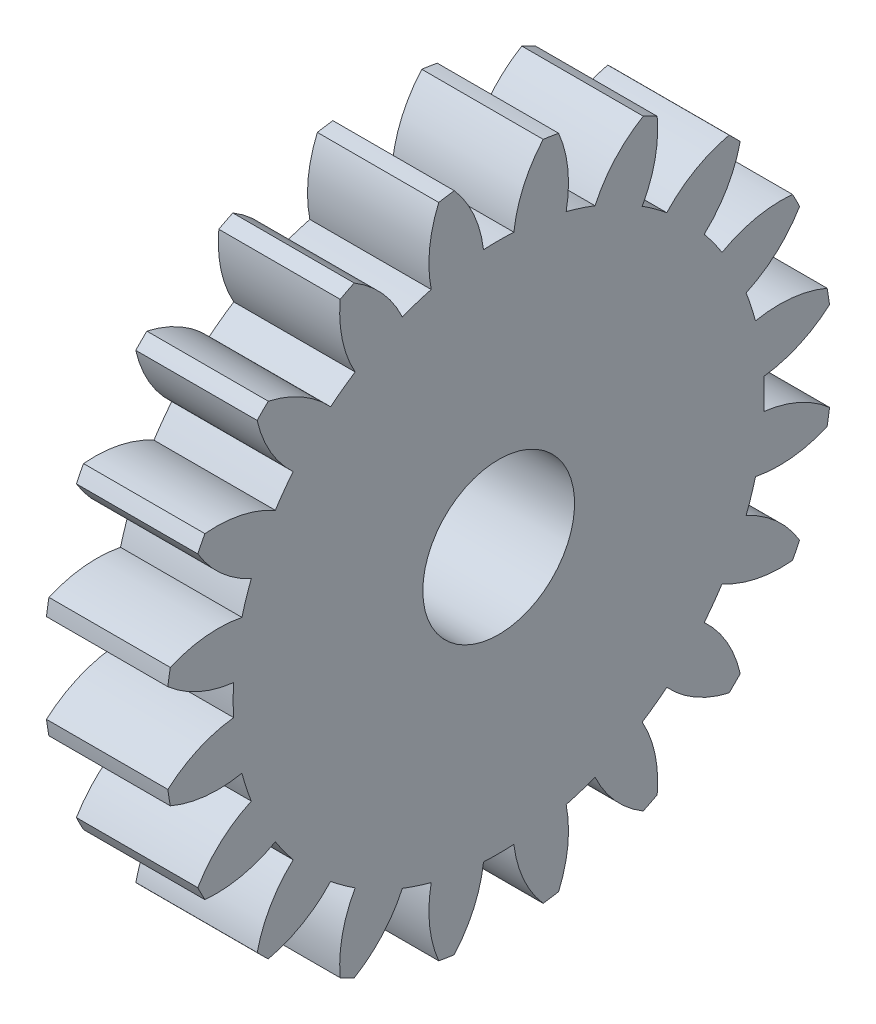
SolidWorks part; units mm, degrees
ref_plane "Plane1" through (0, 0, 0) normal (0, 0, 1) x (1, 0, 0)
ref_plane "Plane2" through (0, 0, 0) normal (0, 1, 0) x (1, 0, 0)
ref_plane "Plane3" through (0, 0, 0) normal (1, 0, 0) x (0, 0, -1)
other "Configuration Table"
sketch "HoldingSke" plane through (0, 0, 0) normal (0, 1, 0) x (1, 0, 0)
  line L0 (0, 0) -> (0.9397, -0.342)
  line L1 (-15, 0) -> (100, 0) construction
  line L2 (0, 0) -> (-2.1039, 2.3779)
  line L3 (0, 0) -> (-11.863, 4.5341)
  line L4 (0, 0) -> (8.1152, 2.9537)
  line L5 (0, 0) -> (-46.8476, -17.4728)
  line L6 (0, 0) -> (-3.3159, -2.2372)
  line L7 (-2.1039, 2.3779) -> (8.6586, 51.2059)
  line L8 (-76.2, 54.61) -> (-75.3, 54.61)
  line L9 (-71.009, 38.7566) -> (-53.1078, 45.2721)
  line L10 (-76.2, 71.12) -> (104.1128, 71.12)
  line L11 (0, 0) -> (-4, 0)
  line L12 (-76.2, 101.6) -> (-76.162, 101.6)
  line L13 (24.9733, 27.94) -> (52.9518, 28.4284)
  line L14 (24.9733, 27.94) -> (24.9743, 27.94)
  line L15 (24.9733, 27.94) -> (100.4006, 29.5858)
  line L16 (-63.627, -1) -> (-12.827, -1)
  circle A0 centre (0, 0) radius 2.5
  circle A1 centre (0, 0) radius 8.749
  circle A2 centre (0, 0) radius 37.5
  circle A3 centre (0, 0) radius 2.5
  dimension "Num_teeth" = 20
  dimension "Pitch_radius" = 180.3128
  dimension "Width" = 4
  dimension "Thickness" = 4
sketch "BasProSke" plane through (0, 0, 0) normal (0, 1, 0) x (1, 0, 0)
  line L0 (-10, 0) -> (60, 0) construction
  line L1 (0, 0) -> (0, 11)
  line L2 (0, 0) -> (4, 0)
  line L3 (4, 0) -> (4, 11)
  line L4 (4, 11) -> (0, 11)
  dimension "Thickness" = 4
  dimension "Diameter" = 22
revolve "Base-Revolve" add sketch "BasProSke" angle 360 about L0
sketch "TooCutSke" plane through (0, 0, 0) normal (1, 0, 0) x (0, 0, -1)
  line L1 (0, 0) -> (0, 107) construction
  line L2 (0, 0) -> (-0.8511, 9.9637) construction
  line L3 (0, 0) -> (-3.1206, 19.7028) construction
  line L4 (-0.8511, 9.9637) -> (-1.5603, 9.8514) construction
  arc A0 (0.4999, 8.7347) -> (-0.4999, 8.7347) centre (0, 0) ccw
  arc A1 (1.4852, 10.9249) -> (-1.4852, 10.9249) centre (0, 0) ccw
  circle A2 centre (0, 0) radius 10 construction
  circle A3 centre (0, 0) radius 9.3969 construction
  arc A4 (-0.4999, 8.7347) -> (-1.4852, 10.9249) centre (-4.4722, 8.2645) ccw
  arc A5 (1.4852, 10.9249) -> (0.4999, 8.7347) centre (4.4722, 8.2645) ccw
extrude "ToothCut" cut sketch "TooCutSke" along normal through all
fillet "Breaks" [suppressed] radius 0.02 tangent propagation no
fillet "RootFillets" [suppressed] radius 0.251
pattern_circular "TeethCuts" count 20 every 18 about axis through (-10, 0, 0) along (1, 0, 0) of "ToothCut", "RootFillets", "Breaks"
sketch "HubNeaOneSke" plane through (0, 0, 0) normal (-1, 0, 0) x (0, 0, 1)
  circle A0 centre (0, 0) radius 8.749
  dimension "Diameter" = 17.498
extrude "HubNearOne" [suppressed] add sketch "HubNeaOneSke" along normal blind 46.0001
sketch "HubNeaBotSke" plane through (0, 0, 0) normal (-1, 0, 0) x (0, 0, 1)
  circle A0 centre (0, 0) radius 8.749
  dimension "Diameter" = 17.498
extrude "HubNearBoth" [suppressed] add sketch "HubNeaBotSke" along normal blind 23
ref_plane "FarPln" through (4, 0, 0) normal (1, 0, 0) x (0, 0, -1)
sketch "HubFarSke" plane through (4, 0, 0) normal (1, 0, 0) x (0, 0, -1)
  circle A0 centre (0, 0) radius 8.749
  dimension "Diameter" = 17.498
extrude "HubFar" [suppressed] add sketch "HubFarSke" along normal blind 23
sketch "BorSke" plane through (0, 0, 0) normal (1, 0, 0) x (0, 0, -1)
  circle A0 centre (0, 0) radius 2.5
  dimension "Diameter" = 5
extrude "Bore" cut sketch "BorSke" along normal mid plane 100.0001
sketch "KeySke" plane through (0, 0, 0) normal (1, 0, 0) x (0, 0, -1)
  line L0 (-1, 0) -> (-1, 3.4)
  line L1 (-1, 3.4) -> (1, 3.4)
  line L2 (1, 3.4) -> (1, 0)
  line L3 (0, 0) -> (0, 34) construction
  line L4 (-1, 0) -> (1, 0)
  dimension "Width" = 2
extrude "Keyway" [suppressed] cut sketch "KeySke" along normal mid plane 100.0001
pattern_circular "Keyway2" [suppressed] count 2 every 90 about axis through (-10, 0, 0) along (1, 0, 0)
equation "' \"Module@HoldingSke\" = 6.35"
equation "' \"Num_teeth@HoldingSke\" = 12"
equation "' \"Ap@HoldingSke\" =  20"
equation "' \"Ap@HoldingSke\" = 20"
equation "' \"Width@HoldingSke\" = 0.5 * 25.4"
equation "' \"Hub_dia@HoldingSke\"= 1 * 25.4"
equation "' \"Hub_dia@HoldingSke\" = 1 * 25.4"
equation "' \"Overall_len@HoldingSke\" = 1.0 * 25.4"
equation "' \"Bore@HoldingSke\" = 0.75 * 25.4"
equation "' \"T_dim@HoldingSke\" = 0.1 * 25.4"
equation "' \"Width@KeySke\" = 0.25 * 25.4"
equation "' \"Show_teeth@HoldingSke\" = 13"
equation "' \"Backlash@HoldingSke\" = 0.009 * 25.4"
equation "' \"Addendum_fac@HoldingSke\" = 1.0"
equation "' \"Dedendum_fac@HoldingSke\" = 1.25"
equation "' \"Dedendum_add@HoldingSke\" = 0.00005 * 25.4"
equation "' \"Clearance_fac@HoldingSke\" = 0.25"
equation "\"Pitch@HoldingSke\" = 1 / \"Module@HoldingSke\""
equation "\"Overcut_dia@TooCutSke\" = (\"Num_teeth@HoldingSke\" + 2 * \"Addendum_fac@HoldingSke\") / \"Pitch@HoldingSke\" + 0.002 * 25.4"
equation "\"Pitch_dia@TooCutSke\" = \"Num_teeth@HoldingSke\" / \"Pitch@HoldingSke\""
equation "\"Base_dia@TooCutSke\" = \"Num_teeth@HoldingSke\" / \"Pitch@HoldingSke\" * cos((\"Ap@HoldingSke\"  * 3.14159265 / 180))"
equation "\"Root_dia@TooCutSke\" = (\"Num_teeth@HoldingSke\" + 2) / \"Pitch@HoldingSke\" - 2 * (\"Addendum_fac@HoldingSke\" + \"Dedendum_fac@HoldingSke\") / \"Pitch@HoldingSke\" - \"Dedendum_add@HoldingSke\" * 2"
equation "\"Half_ang@TooCutSke\" = 180 / \"Num_teeth@HoldingSke\""
equation "\"Half_CT@TooCutSke\" = \"Num_teeth@HoldingSke\" / \"Pitch@HoldingSke\" * sin((3.14159265 / 2 / \"Num_teeth@HoldingSke\")) / 2 - 7 * \"Backlash@HoldingSke\" / 4"
equation "\"Flank_rad@TooCutSke\" = \"Num_teeth@HoldingSke\" / \"Pitch@HoldingSke\" / 5"
equation "\"Radius@RootFillets\" = \"Clearance_fac@HoldingSke\" / \"Pitch@HoldingSke\" + \"Dedendum_add@HoldingSke\""
equation "\"Break_rad@Breaks\" = 0.02 / \"Pitch@HoldingSke\""
equation "\"Thickness@HoldingSke\" = \"Width@HoldingSke\""
equation "\"OAL@HoldingSke\" = \"Thickness@HoldingSke\""
equation "\"MHD@HoldingSke\" = (\"Num_teeth@HoldingSke\" + 2) / \"Pitch@HoldingSke\" - 2 * (\"Addendum_fac@HoldingSke\" + \"Dedendum_fac@HoldingSke\")  / \"Pitch@HoldingSke\" - \"Dedendum_add@HoldingSke\" * 2"
equation "\"MBD@HoldingSke\" = (\"Num_teeth@HoldingSke\" + 2) / \"Pitch@HoldingSke\" - 2 * (\"Addendum_fac@HoldingSke\" + \"Dedendum_fac@HoldingSke\")  / \"Pitch@HoldingSke\" - \"Dedendum_add@HoldingSke\" * 2 - 0.002 * 25.4"
equation "\"MHD@HoldingSke\" = ((sgn( \"MHD@HoldingSke\" - \"Hub_dia@HoldingSke\" )-1)*( \"MHD@HoldingSke\" - \"Hub_dia@HoldingSke\" ))/-2+ \"Hub_dia@HoldingSke\""
equation "\"MBD@HoldingSke\" = ((sgn( \"MBD@HoldingSke\" - \"Bore@HoldingSke\" )-1)*( \"MBD@HoldingSke\" - \"Bore@HoldingSke\" ))/-2+ \"Bore@HoldingSke\""
equation "\"OAL@HoldingSke\" = ((sgn( \"OAL@HoldingSke\" - \"Overall_len@HoldingSke\" )+1)*( \"OAL@HoldingSke\" - \"Overall_len@HoldingSke\" ))/2 + \"Overall_len@HoldingSke\" + 0.000002 * 25.4"
equation "\"Num_teeth@TeethCuts\" = int( \"Show_teeth@HoldingSke\" ) + 1"
equation "\"Num_teeth@TeethCuts\" = ((sgn( \"Num_teeth@TeethCuts\" - \"Num_teeth@HoldingSke\" )-1)*( \"Num_teeth@TeethCuts\" - \"Num_teeth@HoldingSke\" ))/-2+ \"Num_teeth@HoldingSke\""
equation "\"Num_teeth@TeethCuts\" = ((sgn( \"Num_teeth@TeethCuts\" - 2.0)+1)*( \"Num_teeth@TeethCuts\" - 2.0))/2 +2.0"
equation "\"Angle@TeethCuts\" = 360.0 / \"Num_teeth@HoldingSke\""
equation "\"Diameter@BasProSke\" = (\"Num_teeth@HoldingSke\" + 2 * \"Addendum_fac@HoldingSke\") / \"Pitch@HoldingSke\""
equation "\"Thickness@BasProSke\"  = \"Thickness@HoldingSke\""
equation "' \"Fillet_rad@BasProSke\" =  \"Thickness@HoldingSke\" * 0.05"
equation "' \"Fillet_rad@BasProSke\" = \"Thickness@HoldingSke\" * 0.05"
equation "\"MHD@HoldingSke\" = ((sgn( \"MHD@HoldingSke\" - \"Root_dia@TooCutSke\" )-1)*( \"MHD@HoldingSke\" - \"Root_dia@TooCutSke\" ))/-2+ \"Root_dia@TooCutSke\""
equation "\"Diameter@HubNeaOneSke\" = \"MHD@HoldingSke\""
equation "\"Length@HubNearOne\" = \"OAL@HoldingSke\" - \"Thickness@BasProSke\""
equation "\"Diameter@HubNeaBotSke\" = \"MHD@HoldingSke\""
equation "\"Length@HubNearBoth\" = ( \"OAL@HoldingSke\" - \"Thickness@BasProSke\" ) / 2.0"
equation "\"Thickness@FarPln\" = \"Thickness@BasProSke\""
equation "\"Diameter@HubFarSke\" = \"MHD@HoldingSke\""
equation "\"Length@HubFar\" = ( \"OAL@HoldingSke\" - \"Thickness@BasProSke\" ) / 2.0"
equation "\"Diameter@BorSke\" = \"MBD@HoldingSke\""
equation "\"D1@Bore\" = \"OAL@HoldingSke\" * 2.0"
equation "\"D1@Keyway\" = \"OAL@HoldingSke\" * 2.0"
equation "\"Offset@KeySke\" = \"T_dim@HoldingSke\" + \"MBD@HoldingSke\" / 2.0"
